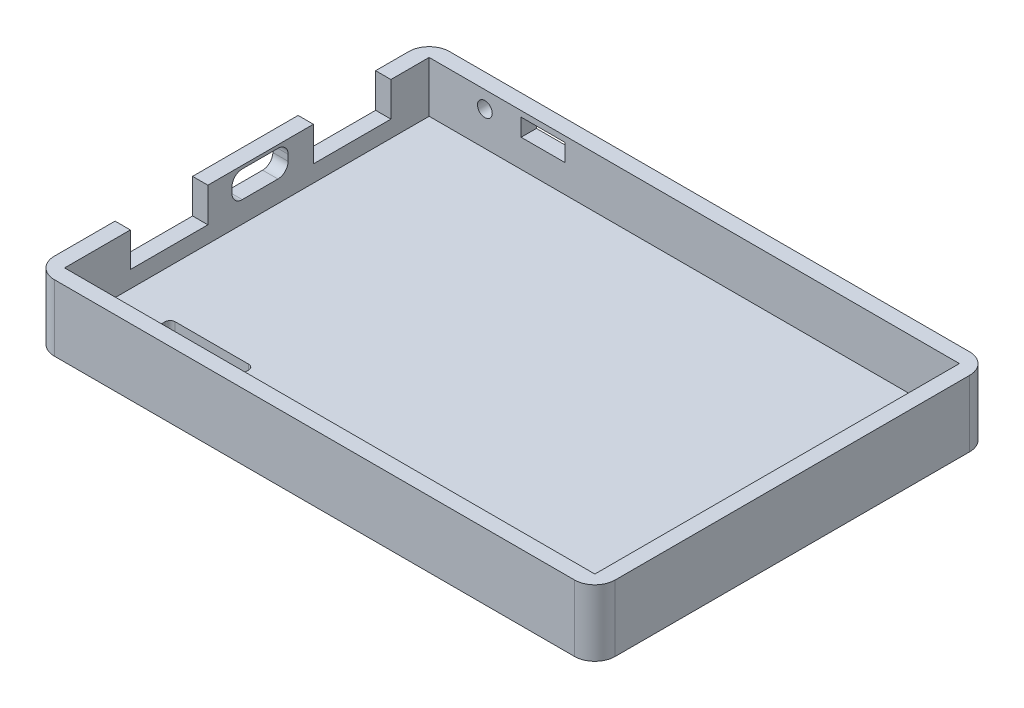
SolidWorks part; units mm, degrees
ref_plane "Front Plane" through (0, 0, 0) normal (0, 0, 1) x (1, 0, 0)
ref_plane "Top Plane" through (0, 0, 0) normal (0, 1, 0) x (1, 0, 0)
ref_plane "Right Plane" through (0, 0, 0) normal (1, 0, 0) x (0, 0, -1)
sketch "Sketch1" plane through (0, 0, 0) normal (0, 1, 0) x (1, 0, 0)
  line L1 (0, 77.5) -> (110, 77.5)
  line L2 (0, 77.5) -> (0, 0)
  line L3 (0, 0) -> (110, 0)
  line L4 (110, 77.5) -> (110, 0)
  line L6 (3, 74.5) -> (3, 3)
  line L7 (3, 3) -> (107, 3)
  line L8 (107, 74.5) -> (107, 3)
  line L9 (3, 74.5) -> (107, 74.5)
  line L10 (0, 73.5) -> (110, 73.5) construction
  line L11 (106, 77.5) -> (106, 0) construction
  dimension "D1" = 3
extrude "Boss-Extrude1" add sketch "Sketch1" along normal blind 10
extrude "Boss-Extrude2" add sketch "Sketch1<2>" against normal blind 3 contours L9 L6 L7 L8 | L4 L1 L2 L3 L6 L9 L8 L7 region at (55, 0, -76.1544) region at (55, 0, -38.75)
sketch "Sketch1<2>" plane through (0, 0, 0) normal (0, 1, 0) x (1, 0, 0) same geometry as "Sketch1"
sketch "Sketch3" plane through (0, 0, 0) normal (-1, 0, 0) x (0, 0, 1)
  line L0 (-66, 10) -> (-66, 4.27) construction
  line L1 (-52.8, 10) -> (-66, 10) construction
  line L2 (-52.8, 10) -> (-52.8, 4.27) construction
  line L3 (-52.8, 4.27) -> (-66, 4.27) construction
  line L4 (-30.1, 10) -> (-30.1, 4.27) construction
  line L5 (-16.9, 4.27) -> (-30.1, 4.27) construction
  line L6 (-16.9, 10) -> (-30.1, 10) construction
  line L7 (-16.9, 10) -> (-16.9, 4.27) construction
  line L8 (-66, 10) -> (-66, 4.27) construction
  line L9 (-52.8, 10) -> (-66, 10) construction
  line L10 (-52.8, 10) -> (-52.8, 4.27) construction
  line L11 (-52.8, 4.27) -> (-66, 4.27) construction
  line L12 (-30.1, 10) -> (-30.1, 4.27) construction
  line L13 (-16.9, 4.27) -> (-30.1, 4.27) construction
  line L14 (-16.9, 10) -> (-30.1, 10) construction
  line L15 (-16.9, 10) -> (-16.9, 4.27) construction
  line L16 (-45.84, 7.38) -> (-45.84, 6.18) construction
  line L17 (-37.84, 8.38) -> (-44.84, 8.38) construction
  line L18 (-36.84, 7.38) -> (-36.84, 6.18) construction
  line L19 (-37.84, 5.18) -> (-44.84, 5.18) construction
  line L20 (-45.84, 7.38) -> (-45.84, 6.18) construction
  line L21 (-37.84, 8.38) -> (-44.84, 8.38) construction
  line L22 (-36.84, 7.38) -> (-36.84, 6.18) construction
  line L23 (-37.84, 5.18) -> (-44.84, 5.18) construction
  line L24 (-15.9, 10) -> (-15.9, 3.27)
  line L25 (-15.9, 3.27) -> (-31.1, 3.27)
  line L26 (-31.1, 10) -> (-31.1, 3.27)
  line L27 (-15.9, 10) -> (-15.9, 3.27) construction
  line L28 (-77.5, 10) -> (0, 10) construction
  line L29 (-31.1, 10) -> (-31.1, 3.27) construction
  line L30 (-51.8, 10) -> (-51.8, 3.27)
  line L31 (-51.8, 3.27) -> (-67, 3.27)
  line L32 (-67, 10) -> (-67, 3.27)
  line L33 (-51.8, 10) -> (-51.8, 3.27) construction
  line L34 (-37.84, 9.38) -> (-44.84, 9.38)
  line L35 (-46.84, 7.38) -> (-46.84, 6.18)
  line L36 (-37.84, 4.18) -> (-44.84, 4.18)
  line L37 (-35.84, 7.38) -> (-35.84, 6.18)
  line L38 (-15.9, 10) -> (-31.1, 10)
  line L39 (-51.8, 10) -> (-67, 10)
  arc A0 (-45.84, 6.18) -> (-44.84, 5.18) centre (-44.84, 6.18) ccw construction
  arc A1 (-44.84, 8.38) -> (-45.84, 7.38) centre (-44.84, 7.38) ccw construction
  arc A2 (-36.84, 7.38) -> (-37.84, 8.38) centre (-37.84, 7.38) ccw construction
  arc A3 (-37.84, 5.18) -> (-36.84, 6.18) centre (-37.84, 6.18) ccw construction
  arc A4 (-45.84, 6.18) -> (-44.84, 5.18) centre (-44.84, 6.18) ccw construction
  arc A5 (-44.84, 8.38) -> (-45.84, 7.38) centre (-44.84, 7.38) ccw construction
  arc A6 (-36.84, 7.38) -> (-37.84, 8.38) centre (-37.84, 7.38) ccw construction
  arc A7 (-37.84, 5.18) -> (-36.84, 6.18) centre (-37.84, 6.18) ccw construction
  arc A8 (-44.84, 9.38) -> (-46.84, 7.38) centre (-44.84, 7.38) ccw
  arc A9 (-46.84, 6.18) -> (-44.84, 4.18) centre (-44.84, 6.18) ccw
  arc A10 (-37.84, 4.18) -> (-35.84, 6.18) centre (-37.84, 6.18) ccw
  arc A11 (-35.84, 7.38) -> (-37.84, 9.38) centre (-37.84, 7.38) ccw
  dimension "D1" = 1
  dimension "D2" = 1
  dimension "D3" = 1
extrude "Cut-Extrude1" cut sketch "Sketch3" against normal up to next
sketch "Sketch4" plane through (0, 0, -77.5) normal (0, 0, -1) x (-1, 0, 0)
  line L0 (-29.14, 8.38) -> (-21.54, 8.38) construction
  line L1 (-29.14, 8.38) -> (-29.14, 5.96) construction
  line L2 (-21.54, 8.38) -> (-21.54, 5.96) construction
  line L3 (-21.54, 5.96) -> (-29.14, 5.96) construction
  line L4 (-29.14, 8.38) -> (-21.54, 8.38) construction
  line L5 (-29.14, 8.38) -> (-29.14, 5.96) construction
  line L6 (-21.54, 8.38) -> (-21.54, 5.96) construction
  line L7 (-21.54, 5.96) -> (-29.14, 5.96) construction
  line L8 (-21.04, 5.46) -> (-29.64, 5.46)
  line L9 (-29.64, 8.88) -> (-29.64, 5.46)
  line L10 (-29.64, 8.88) -> (-21.04, 8.88)
  line L11 (-21.04, 8.88) -> (-21.04, 5.46)
  circle A0 centre (-13.93, 6.69) radius 0.95 construction
  circle A1 centre (-13.93, 6.69) radius 0.95 construction
  circle A2 centre (-13.93, 6.69) radius 1.45
  dimension "D1" = 0.5
extrude "Cut-Extrude2" cut sketch "Sketch4" against normal up to next
sketch "Sketch5" plane through (0, 0, 0) normal (0, 1, 0) x (1, 0, 0)
  line L0 (33.8, 9.2) -> (6.6, 9.2) construction
  line L1 (12, 14.7) -> (28.4, 14.7)
  line L2 (12, 14.7) -> (12, 9.7)
  line L3 (12, 9.7) -> (28.4, 9.7)
  line L4 (28.4, 14.7) -> (28.4, 9.7)
  point P4 (12, 12.2)
  point P5 (20.2, 9.2)
  point P6 (20.2, 9.7)
  point P7 (7, 12.2)
  dimension "D1" = 5
  dimension "D2" = 5
extrude "Cut-Extrude3" cut sketch "Sketch5" against normal through all both and the other way through all
fillet "Fillet1" radius 4 4 edges at (110, 3.5, -77.5) (0, 3.5, -77.5) (110, 3.5, 0) (0, 3.5, 0)
fillet "Fillet2" radius 1 4 edges at (28.4, -1.5, -14.7) (28.4, -1.5, -9.7) (12, -1.5, -9.7) (12, -1.5, -14.7)
